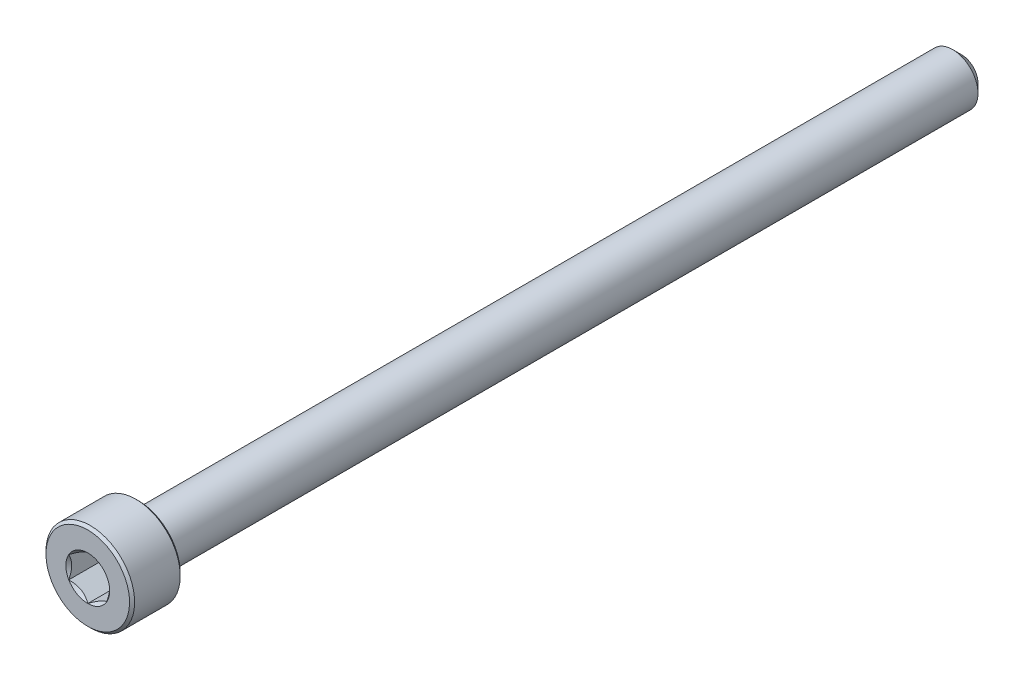
SolidWorks part; units mm, degrees
ref_plane "Front Plane" through (0, 0, 0) normal (0, 0, 1) x (1, 0, 0)
ref_plane "Top Plane" through (0, 0, 0) normal (0, 1, 0) x (1, 0, 0)
ref_plane "Right Plane" through (0, 0, 0) normal (1, 0, 0) x (0, 0, -1)
sketch "Sketch1" plane through (0, 0, 0) normal (1, 0, 0) x (0, 0, -1)
  line L0 (-34.5, 0) -> (34.5, 0) construction
  line L1 (34.5, 0) -> (34.5, 1.3) construction
  line L2 (34.5, 1.3) -> (33.8, 2) construction
  line L3 (33.8, 2) -> (14.5, 2) construction
  line L4 (14.5, 2) -> (-30.5, 2) construction
  line L5 (-30.5, 2) -> (-30.5, 3.5) construction
  line L6 (-30.5, 3.5) -> (-34.5, 3.5) construction
  line L7 (-34.5, 3.5) -> (-34.5, 0) construction
  line L8 (34.5, 1.3) -> (34.5, 2) construction
  line L9 (34.4563, 2.0758) -> (34.8063, 1.4696) construction
  line L10 (34.8063, 1.4696) -> (35.1563, 2.0758) construction
  line L11 (35.1563, 2.0758) -> (34.4563, 2.0758) construction
  line L12 (34.8063, 2.0758) -> (34.8063, 2) construction
  line L13 (34.8063, 1.4696) -> (34.8063, 1.5453) construction
  line L14 (34.7625, 1.5453) -> (34.85, 1.5453) construction
  line L15 (34.5, 2) -> (35.1125, 2) construction
  line L16 (34.4781, 2.0379) -> (35.1344, 2.0379) construction
  line L17 (34.5, 0) -> (34.5, -2) construction
  line L18 (-30.7, 3.5) -> (-30.5, 3.3) construction
  line L19 (-34.3, 3.5) -> (-34.5, 3.3) construction
  line L20 (-30.5, 2) -> (-30.5, 0) construction
  point P0 (-34.5, 1.5)
  point P3 (32.05, 2)
  point P4 (0, 0)
  point P18 (13.5, 2)
  point P22 (34.8063, 1.5453)
  point P24 (14.5, 2)
  point P25 (34.8063, 2)
  point P28 (34.8063, 2.0379)
  point P29 (32.05, -2)
  point P30 (-29.5, 2)
  point P31 (-32.5, 3.5)
  point P37 (-31.2, 3.5)
  point P38 (-34.2, 3.5)
  point P39 (34.5, 0.65)
  dimension "D1" = 45
  dimension "D2" = 0.0875
  dimension "D3" = 0.7
  dimension "D4" = 2.45
  dimension "D5" = 1
  dimension "D6" = 1
  dimension "D7" = 0.2
  dimension "D8" = 0.2
  dimension "D9" = 0.2
  dimension "D10" = 0.1
  dimension "D11" = 0.5
  dimension "Drive Size" = 3
  dimension "Head Diameter" = 7
  dimension "Head Height" = 4
  dimension "Minimum Thread Length" = 20
  dimension "Thread Pitch" = 0.7
  dimension "Thread Major Diameter" = 4
  dimension "Length" = 65
sketch "Sketch2" plane through (0, 0, 0) normal (1, 0, 0) x (0, 0, -1)
  line L0 (-34.5, 0) -> (-34.5, 3.3)
  line L1 (-34.3, 3.5) -> (-30.7, 3.5)
  line L2 (-30.5, 3.3) -> (-30.5, 2)
  line L3 (-30.5, 2) -> (33.8, 2)
  line L4 (33.8, 2) -> (34.5, 1.3)
  line L5 (34.5, 1.3) -> (34.5, 0)
  line L6 (-30.7, 3.5) -> (-30.5, 3.3) construction
  line L7 (34.5, 0) -> (-34.5, 0)
  line L8 (-34.3, 3.5) -> (-34.5, 3.3) construction
  line L9 (-30.7, 3.5) -> (-30.5, 3.3)
  line L10 (-34.3, 3.5) -> (-34.5, 3.3)
revolve "Revolve1" add sketch "Sketch2" angle 360 about L7
sketch "Sketch3" plane through (0, 0, 34.5) normal (0, 0, 1) x (1, 0, 0)
  line L1 (1.5, -0.866) -> (1.5, 0.866)
  line L2 (1.5, 0.866) -> (0, 1.7321)
  line L3 (0, 1.7321) -> (-1.5, 0.866)
  line L4 (-1.5, 0.866) -> (-1.5, -0.866)
  line L5 (-1.5, -0.866) -> (0, -1.7321)
  line L6 (0, -1.7321) -> (1.5, -0.866)
  circle A0 centre (0, 0) radius 1.5 construction
extrude "Cut-Extrude1" cut sketch "Sketch3" against normal offset from surface (3 mm away) 1 up to face at (0, 3.3, 30.5)
sketch "Sketch4" plane through (0, 0, 34.5) normal (0, 0, 1) x (1, 0, 0)
  circle A0 centre (0, 0) radius 1.7321
extrude "Cut-Extrude2" cut sketch "Sketch4" against normal up to vertex (2 mm away) draft 45 up to point (0, 3.5, 32.5)
ref_plane "Plane1" [suppressed] through (0, 0, -14.5) normal (0, 0, 1) x (1, 0, 0)
split "Split1" [suppressed] bodies to split 106
sketch "Sketch6" [suppressed] plane through (0, 0, -34.5) normal (0, 0, -1) x (-1, 0, 0)
  circle A0 centre (0, 0) radius 2
curve "Helix/Spiral1" [suppressed] pitch 0.7 height 20.7 turns 29.5714
sketch "Sketch7" [suppressed] plane through (0, 0, 0) normal (1, 0, 0) x (0, 0, -1)
  line L0 (34.4781, 2.0379) -> (35.1344, 2.0379)
  line L1 (35.1344, 2.0379) -> (34.85, 1.5453)
  line L2 (34.85, 1.5453) -> (34.7625, 1.5453)
  line L3 (34.7625, 1.5453) -> (34.4781, 2.0379)
sweep "Cut-Sweep1" [suppressed] cut profiles "Sketch7" path "Helix/Spiral1"
sketch "Sketch8" [suppressed] plane through (0, 0, -14.5) normal (0, 0, -1) x (-1, 0, 0)
  circle A0 centre (0, 0) radius 2
extrude "Boss-Extrude1" [suppressed] add sketch "Sketch8" along normal through all draft 45
equation "\"D2@Sketch1\" = \"Thread Pitch@Sketch1\" / 8"
equation "\"D3@Sketch1\"= \"Thread Pitch@Sketch1\""
equation "\"D3@Helix/Spiral1\" = \"Minimum Thread Length@Sketch1\" + \"Thread Pitch@Sketch1\""
equation "\"D4@Helix/Spiral1\" = \"Thread Pitch@Sketch1\""
equation "\"D4@Sketch1\" = \"Thread Pitch@Sketch1\" * 3.5"
equation "\"D7@Sketch1\" = \"Head Height@Sketch1\" * .05"
equation "\"D8@Sketch1\"=\"D7@Sketch1\""
equation "\"D9@Sketch1\"=\"D7@Sketch1\""
equation "\"D10@Sketch1\"=\"D7@Sketch1\"/2"
equation "\"D11@Sketch1\"=\"D10@Sketch1\"*5"
